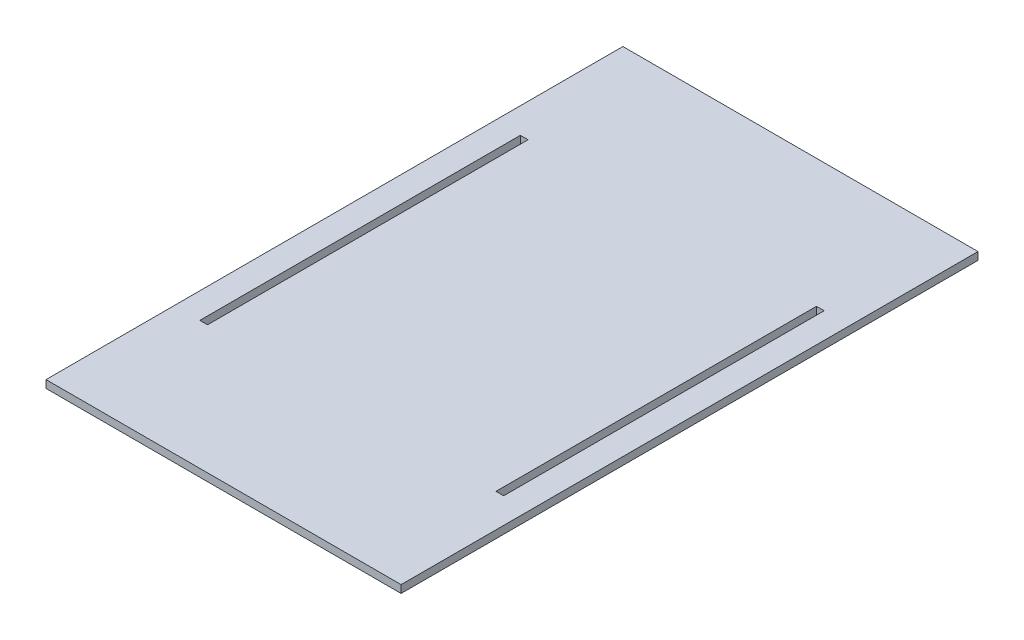
SolidWorks part; units mm, degrees
ref_plane "Front Plane" through (0, 0, 0) normal (0, 0, 1) x (1, 0, 0)
ref_plane "Top Plane" through (0, 0, 0) normal (0, 1, 0) x (1, 0, 0)
ref_plane "Right Plane" through (0, 0, 0) normal (1, 0, 0) x (0, 0, -1)
sketch "Sketch1" plane through (0, 0, 0) normal (0, 0, 1) x (1, 0, 0)
  line L1 (19.86, -14.9279) -> (-257.14, -14.9279)
  line L2 (19.86, -14.9279) -> (19.86, -8.9279)
  line L3 (19.86, -8.9279) -> (-257.14, -8.9279)
  line L4 (-257.14, -14.9279) -> (-257.14, -8.9279)
  line L5 (19.86, -14.9279) -> (-257.14, -8.9279) construction
  line L6 (19.86, -8.9279) -> (-257.14, -14.9279) construction
  point P0 (-118.64, -11.9279)
extrude "Boss-Extrude1" add sketch "Sketch1" along normal blind 450
sketch "Sketch2" plane through (0, -8.9279, 0) normal (0, 1, 0) x (1, 0, 0)
  line L0 (19.86, -450) -> (-257.14, -450) construction
  line L1 (-237.14, -100) -> (-231.14, -100)
  line L2 (-237.14, -100) -> (-237.14, -350)
  line L3 (-237.14, -350) -> (-231.14, -350)
  line L4 (-231.14, -100) -> (-231.14, -350)
  line L5 (-6.14, -100) -> (-0.14, -100)
  line L6 (-6.14, -100) -> (-6.14, -350)
  line L7 (-6.14, -350) -> (-0.14, -350)
  line L8 (-0.14, -100) -> (-0.14, -350)
  line L9 (19.86, 0) -> (-257.14, 0) construction
  line L10 (-257.14, -450) -> (-257.14, 0) construction
  line L11 (19.86, -450) -> (19.86, 0) construction
  dimension "D1" = 100
  dimension "D2" = 100
  dimension "D3" = 100
  dimension "D4" = 100
  dimension "D5" = 20
  dimension "D6" = 20
  dimension "D7" = 6
  dimension "D8" = 6
extrude "Cut-Extrude1" cut sketch "Sketch2" against normal up to next
